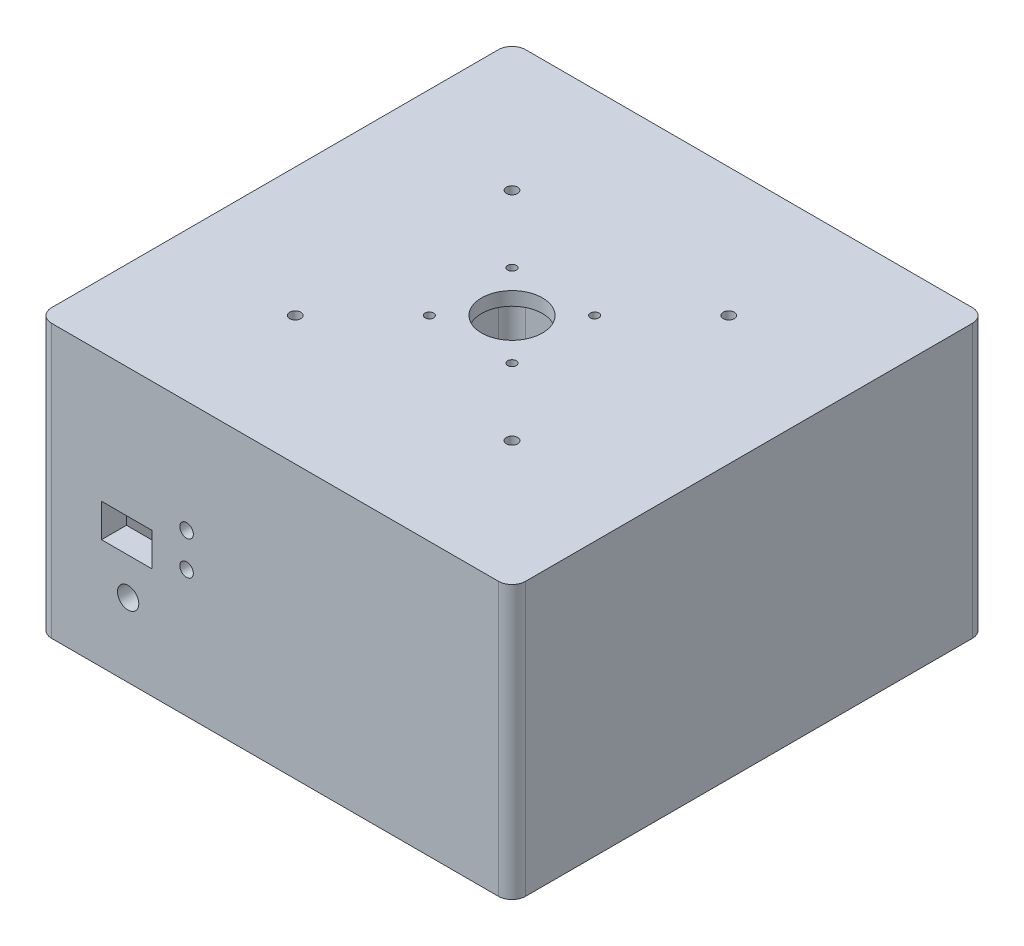
SolidWorks part; units mm, degrees
ref_plane "Front Plane" through (0, 0, 0) normal (0, 0, 1) x (1, 0, 0)
ref_plane "Top Plane" through (0, 0, 0) normal (0, 1, 0) x (1, 0, 0)
ref_plane "Right Plane" through (0, 0, 0) normal (1, 0, 0) x (0, 0, -1)
sketch "Sketch1" plane through (0, 0, 0) normal (0, 1, 0) x (1, 0, 0)
  line L1 (-83.82, -88.9) -> (83.82, -88.9)
  line L2 (-88.9, -83.82) -> (-88.9, 83.82)
  line L3 (-83.82, 88.9) -> (83.82, 88.9)
  line L4 (88.9, -83.82) -> (88.9, 83.82)
  line L5 (-88.9, -88.9) -> (88.9, 88.9) construction
  line L6 (-88.9, 88.9) -> (88.9, -88.9) construction
  line L11 (-64.7359, -64.7359) -> (-18.5761, -18.5761) construction
  line L12 (-23.0799, 23.0799) -> (23.0799, -23.0799) construction
  line L13 (-79.5394, -79.5394) -> (79.5394, -79.5394)
  line L14 (-79.5394, -79.5394) -> (-79.5394, 79.5394)
  line L15 (-79.5394, 79.5394) -> (79.5394, 79.5394)
  line L16 (79.5394, -79.5394) -> (79.5394, 79.5394)
  line L17 (-79.5394, -79.5394) -> (79.5394, 79.5394) construction
  line L18 (-79.5394, 79.5394) -> (79.5394, -79.5394) construction
  circle A0 centre (0, 0) radius 11.43
  arc A1 (-83.82, -88.9) -> (-88.9, -83.82) centre (-83.82, -83.82) cw
  arc A2 (83.82, -88.9) -> (88.9, -83.82) centre (83.82, -83.82) ccw
  arc A3 (83.82, 88.9) -> (88.9, 83.82) centre (83.82, 83.82) cw
  arc A4 (-88.9, 83.82) -> (-83.82, 88.9) centre (-83.82, 83.82) cw
  point P0 (0, 0)
  point P6 (0, 0)
  point P11 (0, 0)
  dimension "D3" = 22.86
  dimension "D2" = 5.08
  dimension "D1" = 177.8
extrude "Boss-Extrude1" add sketch "Sketch1" along normal blind 38.1 and the other way blind 59.182 contours L1 L4 L3 L2 L16 L13 L14 L15 region at (-85.6341, 0, 85.6341)
extrude "Boss-Extrude3" add sketch "Sketch1<5>" along normal blind 5.08 from surface contours L1 L4 L3 L2 L16 L13 L14 L15 | L13 L16 L15 L14 region at (-85.6341, 0, 85.6341) region at (-77.2897, 0, 0) starting at face at (0, 38.1, 0)
sketch "Sketch1<5>" plane through (0, 0, 0) normal (0, 1, 0) x (1, 0, 0) same geometry as "Sketch1"
sketch "Sketch3" plane through (0, 43.18, 0) normal (0, 1, 0) x (1, 0, 0)
  line L0 (0, 88.9) -> (0, -88.9) construction
  line L2 (-88.9, 0) -> (88.9, 0) construction
  line L3 (88.9, 83.82) -> (88.9, -83.82) construction
  line L4 (83.82, -88.9) -> (-83.82, -88.9) construction
  circle A0 centre (-15.5, 15.5) radius 1.6
  circle A1 centre (-15.5, -15.5) radius 1.6
  circle A2 centre (15.5, 15.5) radius 1.6
  circle A3 centre (15.5, -15.5) radius 1.6
  point P7 (0, 0)
  point P14 (0, 0)
  point P15 (0, 0)
  dimension "D1" = 3.2
  dimension "D2" = 15.5
  dimension "D3" = 15.5
extrude "Cut-Extrude1" cut sketch "Sketch3" against normal through all
fillet "Fillet4" radius 5.08 4 edges at (-79.5394, -10.541, -79.5394) (-79.5394, -10.541, 79.5394) (79.5394, -10.541, 79.5394) (79.5394, -10.541, -79.5394)
sketch "Sketch4" plane through (0, 43.18, 0) normal (0, 1, 0) x (1, 0, 0)
  line L0 (0, 88.9) -> (0, -88.9) construction
  line L1 (83.82, -88.9) -> (-83.82, -88.9) construction
  line L2 (-88.9, 0) -> (88.9, 0) construction
  line L3 (88.9, 83.82) -> (88.9, -83.82) construction
  circle A0 centre (-40.66, 40.66) radius 2.1
  circle A1 centre (40.66, 40.66) radius 2.1
  circle A2 centre (-40.66, -40.66) radius 2.1
  circle A3 centre (40.66, -40.66) radius 2.1
  point P7 (0, 0)
  point P14 (0, 0)
  dimension "D1" = 4.2
  dimension "D2" = 40.66
  dimension "D3" = 40.66
extrude "Cut-Extrude2" cut sketch "Sketch4" against normal up to surface (5.08 mm away) up to face at (15.5, 38.1, 17.1)
sketch "Sketch5" plane through (0, 0, 88.9) normal (0, 0, 1) x (1, 0, 0)
  line L1 (-65.0849, -5.263) -> (-46.0849, -5.263)
  line L2 (-65.0849, -5.263) -> (-65.0849, -17.763)
  line L3 (-65.0849, -17.763) -> (-46.0849, -17.763)
  line L4 (-46.0849, -5.263) -> (-46.0849, -17.763)
  circle A0 centre (-33.1876, -11.513) radius 2.54
  circle A1 centre (-33.1876, 1.2065) radius 2.54
  circle A2 centre (-55.1023, -31.6253) radius 4
  point P7 (-46.0849, -11.513)
  dimension "D3" = 5.08
  dimension "D1" = 19
  dimension "D2" = 12.5
extrude "Cut-Extrude3" cut sketch "Sketch5" against normal up to surface (9.3606 mm away) up to face at (0, -10.541, 79.5394)
sketch "Sketch7" plane through (0, -59.182, 0) normal (0, -1, 0) x (1, 0, 0)
  line L0 (-74.4594, -79.5394) -> (74.4594, -79.5394) construction
  line L1 (-12.7, -84.6194) -> (12.7, -84.6194)
  line L2 (-12.7, -84.6194) -> (-12.7, -79.5394)
  line L3 (-12.7, -79.5394) -> (12.7, -79.5394)
  line L4 (12.7, -84.6194) -> (12.7, -79.5394)
  line L5 (-12.7, -84.6194) -> (12.7, -79.5394) construction
  line L6 (-12.7, -79.5394) -> (12.7, -84.6194) construction
  point P0 (0, -82.0794)
  dimension "D1" = 5.08
  dimension "D2" = 25.4
extrude "Cut-Extrude4" cut sketch "Sketch7" against normal blind 5.588
sketch "Sketch10" plane through (12.7, 0, 0) normal (-1, 0, 0) x (0, 0, 1)
  line L0 (-79.5394, -46.736) -> (-79.5394, -49.53)
  line L1 (-81.0634, -49.53) -> (-79.5394, -49.53)
  line L3 (-79.5394, -59.182) -> (-79.5394, 38.1) construction
  line L4 (-81.0634, -49.53) -> (-79.5394, -46.736)
  dimension "D1" = 0
  dimension "D2" = 9.652
  dimension "D3" = 2.794
  dimension "D4" = 1.524
extrude "Boss-Extrude4" add sketch "Sketch10" along normal up to surface (25.4 mm away) up to face at (-12.7, -56.388, -82.0794)
extrude "Cut-Extrude5" cut sketch "Sketch10<2>" along normal up to surface (25.4 mm away) up to face at (-12.7, -56.388, -82.0794)
sketch "Sketch10<2>" plane through (12.7, 0, 0) normal (-1, 0, 0) x (0, 0, 1) same geometry as "Sketch10"
sketch "Sketch11" plane through (0, 0, 79.5394) normal (0, 0, -1) x (-1, 0, 0)
  line L1 (-50.8, -54.102) -> (-38.1, -54.102)
  line L2 (-50.8, -54.102) -> (-50.8, -49.53)
  line L3 (-50.8, -49.53) -> (-38.1, -49.53)
  line L4 (-38.1, -54.102) -> (-38.1, -49.53)
  line L5 (83.82, -59.182) -> (-83.82, -59.182) construction
  line L6 (0, -59.182) -> (0, -21.4618) construction
  line L7 (38.1, -54.102) -> (38.1, -49.53)
  line L8 (50.8, -49.53) -> (38.1, -49.53)
  line L9 (50.8, -54.102) -> (50.8, -49.53)
  line L10 (50.8, -54.102) -> (38.1, -54.102)
  dimension "D1" = 12.7
  dimension "D2" = 4.572
  dimension "D3" = 5.08
  dimension "D4" = 38.1
extrude "Cut-Extrude6" cut sketch "Sketch11" against normal blind 5.334
